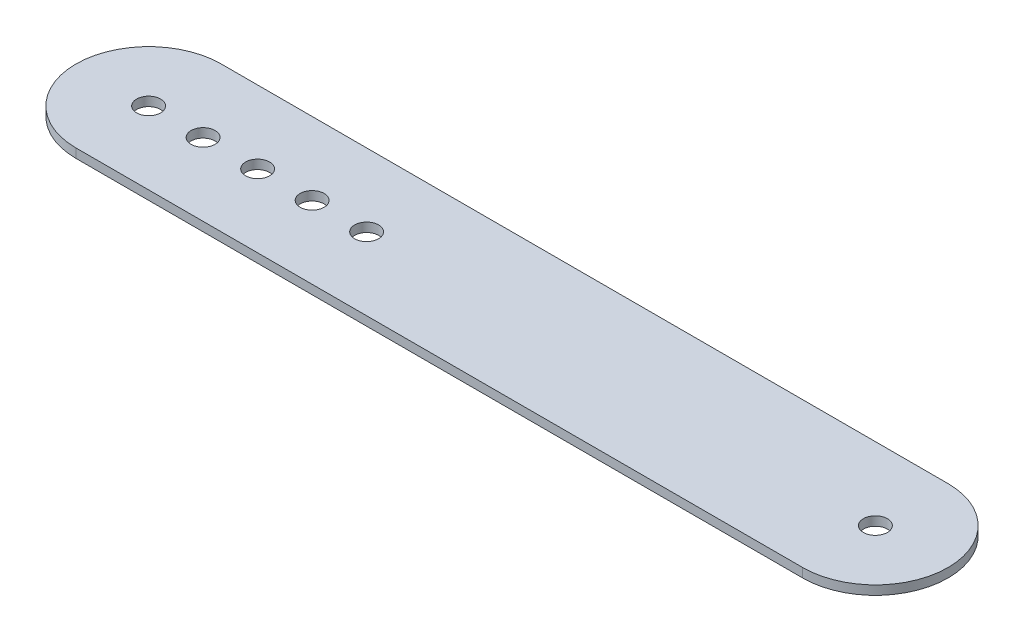
SolidWorks part; units mm, degrees
ref_plane "Front Plane" through (0, 0, 0) normal (0, 0, 1) x (1, 0, 0)
ref_plane "Top Plane" through (0, 0, 0) normal (0, 1, 0) x (1, 0, 0)
ref_plane "Right Plane" through (0, 0, 0) normal (1, 0, 0) x (0, 0, -1)
sketch "Sketch1" plane through (0, 0, 0) normal (0, 1, 0) x (1, 0, 0)
  line L0 (0, 0) -> (-254, 0) construction
  line L1 (0, 25.4) -> (-254, 25.4)
  line L2 (0, -25.4) -> (-254, -25.4)
  arc A0 (0, -25.4) -> (0, 25.4) centre (0, 0) ccw
  arc A1 (-254, 25.4) -> (-254, -25.4) centre (-254, 0) ccw
  dimension "D1" = 50.8
  dimension "D2" = 254
extrude "Boss-Extrude1" add sketch "Sketch1" along normal blind 3.175
sketch "Sketch3" plane through (0, 3.175, 0) normal (0, 1, 0) x (1, 0, 0)
  circle A0 centre (0, 0) radius 4.191
  circle A1 centre (-254, 0) radius 4.191
  dimension "D1" = 8.382
extrude "Cut-Extrude1" cut sketch "Sketch3" against normal through all contours A0 | A1
pattern_linear "LPattern1" count 5 spacing 19.05 along (1, 0, 0) of face at (-254, 0, 4.191)
